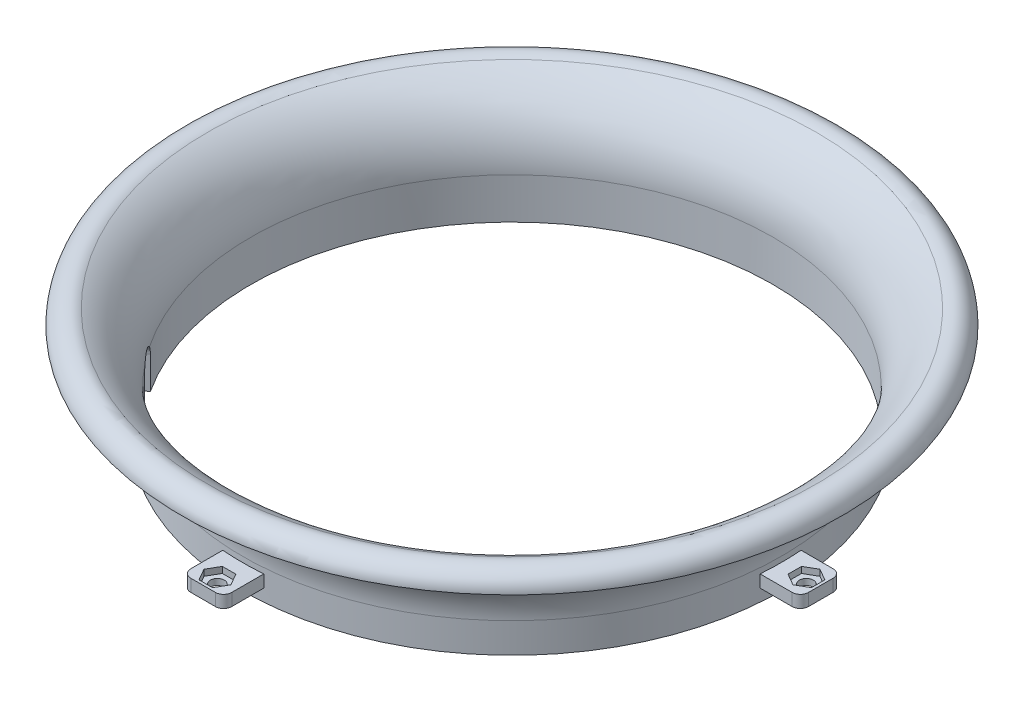
SolidWorks part; units mm, degrees
note: '?' marks a value the reader was unsure of.
ref_plane "Front Plane" through (0, 0, 0) normal (0, 0, 1) x (1, 0, 0)
ref_plane "Top Plane" through (0, 0, 0) normal (0, 1, 0) x (1, 0, 0)
ref_plane "Right Plane" through (0, 0, 0) normal (1, 0, 0) x (0, 0, -1)
sketch "Sketch1" plane through (0, 0, 0) normal (0, 0, 1) x (1, 0, 0)
  line L0 (0, 0) -> (0, 46.3379) construction
  line L1 (63.75, 18.737) -> (63.75, 25.0985)
  line L2 (63.75, 18.737) -> (65.75, 18.737) construction
  line L3 (63.75, 18.737) -> (63.75, 15.0985)
  line L4 (63.75, 15.0985) -> (65.75, 15.0985)
  line L5 (65.75, 18.737) -> (65.75, 22.4073)
  line L6 (-215.8183, -73.5249) -> (31.111, -73.5249) construction
  line L7 (65.75, 15.0985) -> (65.75, 18.737)
  arc A0 (63.75, 25.0985) -> (74.3195, 41.9837) centre (82.5222, 25.0985) cw
  arc A1 (74.3195, 41.9837) -> (80.4259, 38.2396) centre (76.1766, 38.1609) cw
  arc A2 (80.4259, 38.2396) -> (65.75, 22.4073) centre (81.6278, 22.4073) ccw
  dimension "D5" = 10
  dimension "D2" = 4.25
  dimension "D4" = 15.8778
  dimension "D1" = 2
  dimension "D3" = 63.75
revolve "Revolve1" add sketch "Sketch1" angle 360 about L0
ref_plane "Plane1" through (0, 18.0985, 0) normal (0, -1, 0) x (-1, 0, 0)
sketch "Sketch3" plane through (0, 18.0985, 0) normal (0, -1, 0) x (-1, 0, 0)
  line L0 (65.5596, 5) -> (65.5596, -5) construction
  line L1 (65.5596, 5) -> (73.3696, 5)
  line L2 (65.5596, -5) -> (73.3696, -5)
  line L3 (75.3696, 3) -> (75.3696, -3)
  line L4 (75.3696, 0) -> (0, 0) construction
  arc A0 (65.5596, 5) -> (65.5596, -5) centre (0, 0) cw
  arc A1 (73.3696, 5) -> (75.3696, 3) centre (73.3696, 3) cw
  arc A2 (73.3696, -5) -> (75.3696, -3) centre (73.3696, -3) ccw
  circle A3 centre (0, 0) radius 65.75 construction
  circle A4 centre (0, 0) radius 65.75 construction
  point P11 (75.3696, 5)
  point P14 (75.3696, -5)
  dimension "D3" = 2
  dimension "D1" = 9.81
  dimension "D2" = 10
extrude "Boss-Extrude1" add sketch "Sketch3" against normal blind 3
sketch "Sketch5" plane through (0, 21.0985, 0) normal (0, 1, 0) x (1, 0, 0)
  line L1 (-75.3696, -3) -> (-75.3696, 3) construction
  line L2 (-75.3696, 0) -> (-66.9184, 0) construction
  circle A0 centre (-71.8696, 0) radius 1.7
  dimension "D2" = 3.4
  dimension "D1" = 3.5
extrude "Cut-Extrude2" cut sketch "Sketch5" against normal through all
sketch "Sketch4" plane through (0, 21.0985, 0) normal (0, 1, 0) x (1, 0, 0)
  line L0 (-74.3195, 0) -> (-69.4197, 0) construction
  line L2 (-71.8696, 3.2909) -> (-74.7196, 1.6454)
  line L3 (-74.7196, 1.6454) -> (-74.7196, -1.6454)
  line L4 (-74.7196, -1.6454) -> (-71.8696, -3.2909)
  line L5 (-71.8696, -3.2909) -> (-69.0196, -1.6454)
  line L6 (-69.0196, -1.6454) -> (-69.0196, 1.6454)
  line L7 (-69.0196, 1.6454) -> (-71.8696, 3.2909)
  circle A0 centre (0, 0) radius 74.3195 construction
  circle A1 centre (-71.8696, 0) radius 2.85 construction
  circle A2 centre (-71.8696, 0) radius 1.7 construction
  dimension "D1" = 5.7
extrude "Cut-Extrude1" cut sketch "Sketch4" against normal blind 1.5
pattern_circular "CirPattern13" count 4 over 360 about axis through (0, 0, 0) along (0, 1, 0) of "Boss-Extrude1", "Cut-Extrude2", "Cut-Extrude1"
ref_axis "Center Axis" through (0, -7.2671, 0) along (0, 1, 0)?
ref_plane "Reference Plane1" through (0, 0, 0) normal (0.866, 0, -0.5) x (0, 1, 0)
ref_plane "WireHole Plane" through (0, 0, 0) normal (0.809, 0, -0.5878) x (0, 1, 0)
sketch "Sketch6" plane through (0, 0, 0) normal (0.809, 0, -0.5878) x (0, 1, 0)
  line L0 (21, 0) -> (23, 0) construction
  line L1 (21, 3.175) -> (23, 3.175) construction
  line L2 (21, -3.175) -> (23, -3.175) construction
  line L3 (21, 3.175) -> (15.0985, 3.175)
  line L4 (15.0985, 65.75) -> (15.0985, -65.75) construction
  line L5 (21, -3.175) -> (15.0985, -3.175)
  line L6 (15.0985, -3.175) -> (15.0985, 3.175)
  line L7 (21, 3.175) -> (23, 3.175)
  line L8 (21, -3.175) -> (23, -3.175)
  arc A0 (21, 3.175) -> (21, -3.175) centre (21, 0) ccw construction
  arc A1 (23, -3.175) -> (23, 3.175) centre (23, 0) ccw construction
  arc A2 (23, 3.175) -> (23, -3.175) centre (23, 0) cw
  point P2 (22, 0)
  dimension "D1" = 3.175
  dimension "D2" = 2
  dimension "D3" = 22
extrude "Cut-Extrude3" cut sketch "Sketch6" against normal through all
ref_plane "Plane4" through (0, 38, 0) normal (0, 1, 0) x (1, 0, 0)
